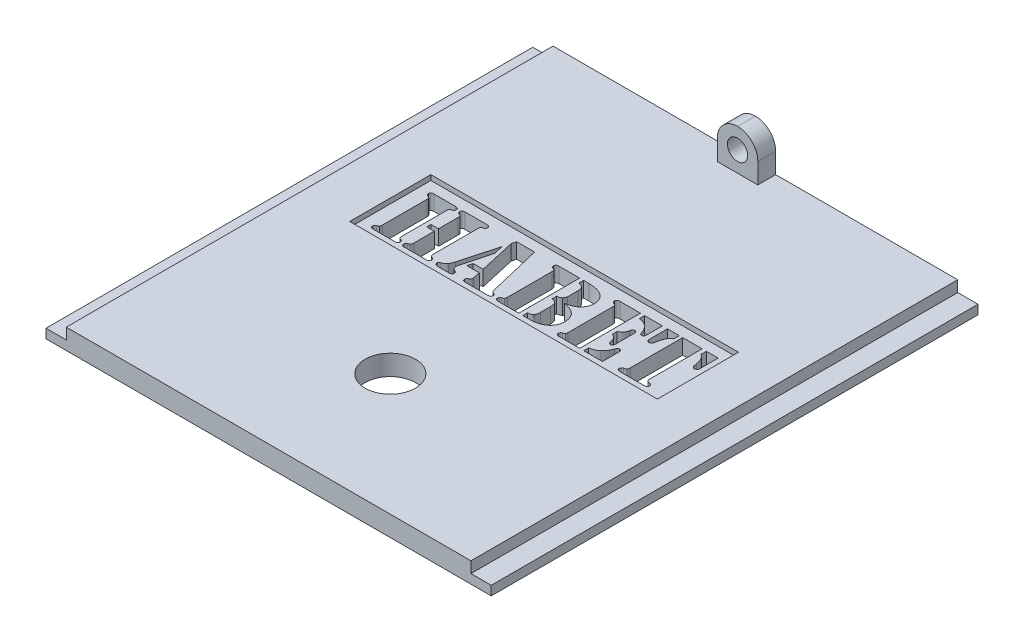
SolidWorks part; units mm, degrees
ref_plane "Front Plane" through (0, 0, 0) normal (0, 0, 1) x (1, 0, 0)
ref_plane "Top Plane" through (0, 0, 0) normal (0, 1, 0) x (1, 0, 0)
ref_plane "Right Plane" through (0, 0, 0) normal (1, 0, 0) x (0, 0, -1)
sketch "Sketch1" plane through (0, 0, 0) normal (0, 1, 0) x (1, 0, 0)
  line L1 (0, 0) -> (139.4003, 0)
  line L2 (0, 0) -> (0, 152.4)
  line L3 (0, 152.4) -> (139.4003, 152.4)
  line L4 (139.4003, 0) -> (139.4003, 152.4)
  dimension "D1" = 152.4
  dimension "D2" = 139.4003
extrude "Boss-Extrude1" add sketch "Sketch1" along normal blind 6.35
sketch "Sketch2" plane through (0, 6.35, 0) normal (0, 1, 0) x (1, 0, 0)
  line L0 (0, 0) -> (139.4003, 0) construction
  line L1 (0, 152.4) -> (6.35, 152.4)
  line L2 (0, 152.4) -> (0, 0)
  line L3 (0, 0) -> (6.35, 0)
  line L4 (6.35, 152.4) -> (6.35, 0)
  line L6 (139.4003, 152.4) -> (133.0503, 152.4)
  line L7 (139.4003, 152.4) -> (139.4003, 0)
  line L8 (139.4003, 0) -> (133.0503, 0)
  line L9 (133.0503, 152.4) -> (133.0503, 0)
  dimension "D1" = 6.35
  dimension "D2" = 6.35
extrude "Cut-Extrude1" cut sketch "Sketch2" against normal blind 3.4747
sketch "Sketch3" plane through (0, 6.35, 0) normal (0, 1, 0) x (1, 0, 0)
  line L0 (133.0503, 152.4) -> (6.35, 152.4) construction
  line L1 (63.3501, 152.4) -> (76.0501, 152.4)
  line L2 (63.3501, 152.4) -> (63.3501, 146.8137)
  line L3 (63.3501, 146.8137) -> (76.0501, 146.8137)
  line L4 (76.0501, 152.4) -> (76.0501, 146.8137)
  point P6 (69.7001, 152.4)
  point P7 (69.7001, 152.4)
  dimension "D1" = 12.7
extrude "Boss-Extrude2" add sketch "Sketch3" along normal blind 12.7
fillet "Fillet1" radius 6.35 2 edges at (63.3501, 19.05, -149.6068) (76.0501, 19.05, -149.6068)
sketch "Sketch4" plane through (0, 0, -152.4) normal (0, 0, -1) x (-1, 0, 0)
  circle A0 centre (-69.7001, 12.7) radius 3.175
  arc A1 (-63.3501, 12.7) -> (-69.7001, 19.05) centre (-69.7001, 12.7) ccw construction
  dimension "D1" = 3.175
extrude "Cut-Extrude2" cut sketch "Sketch4" against normal blind 6.35
sketch "Sketch7" plane through (0, 6.35, 0) normal (0, 1, 0) x (1, 0, 0)
  line L0 (6.35, 76.2) -> (133.0503, 76.2) construction
  line L3 (6.35, 0) -> (6.35, 152.4) construction
  line L4 (133.0503, 152.4) -> (133.0503, 0) construction
  text T0 "HABET" font "Stencil" height 19.05
extrude "Cut-Extrude7" cut sketch "Sketch7" against normal blind 6.35
sketch "Sketch9" plane through (0, 6.35, 0) normal (0, 1, 0) x (1, 0, 0)
  line L0 (35.9699, 95.25) -> (42.8243, 95.25) construction
  line L1 (22.0751, 98.425) -> (118.3835, 98.425)
  line L2 (22.0751, 98.425) -> (22.0751, 73.025)
  line L3 (22.0751, 73.025) -> (118.3835, 73.025)
  line L4 (118.3835, 98.425) -> (118.3835, 73.025)
  line L5 (42.8243, 76.2) -> (35.941, 76.2) construction
  line L6 (115.2085, 95.25) -> (115.2085, 89.5036) construction
  point P7 (39.3971, 95.25)
  point P10 (39.3826, 76.2)
  dimension "D1" = 3.175
  dimension "D2" = 3.175
  dimension "D3" = 3.175
  dimension "D4" = 3.175
extrude "Cut-Extrude8" cut sketch "Sketch9" against normal blind 1.5875
sketch "Sketch10" plane through (0, 6.35, 0) normal (0, 1, 0) x (1, 0, 0)
  line L0 (6.35, 0) -> (133.0503, 0) construction
  circle A0 centre (69.7001, 38.1) radius 7.874
  point P4 (0, 0)
  point P5 (69.7001, 0)
  dimension "D1" = 15.748
  dimension "D2" = 38.1
extrude "Cut-Extrude9" cut sketch "Sketch10" against normal through all
